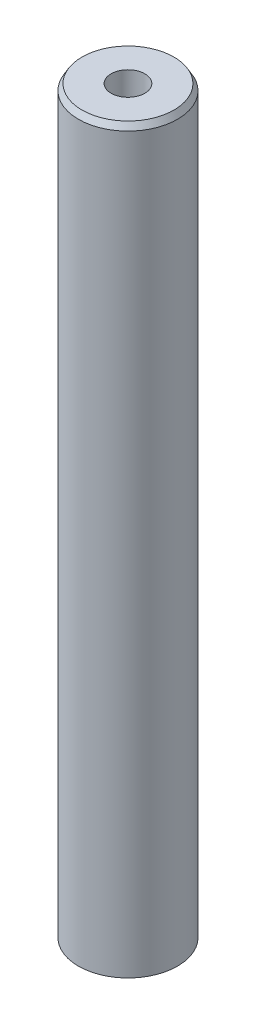
SolidWorks part; units mm, degrees
ref_plane "Front Plane" through (0, 0, 0) normal (0, 0, 1) x (1, 0, 0)
ref_plane "Top Plane" through (0, 0, 0) normal (0, 1, 0) x (1, 0, 0)
ref_plane "Right Plane" through (0, 0, 0) normal (1, 0, 0) x (0, 0, -1)
sketch "Sketch1" plane through (0, 0, 0) normal (0, 1, 0) x (1, 0, 0)
  circle A0 centre (0, 0) radius 40
  dimension "SHAFT_OD" = 80
extrude "Boss-Extrude1" add sketch "Sketch1" along normal blind 600
sketch "Sketch2" plane through (0, 0, 0) normal (0, 1, 0) x (1, 0, 0)
  circle A0 centre (0, 0) radius 13.6341
  dimension "BORE_D" = 27.2682
extrude "Cut-Extrude1" cut sketch "Sketch2" along normal through all
chamfer "Chamfer1" distance 5.0049 angle 30 2 edges at (0, 600, 40) (0, 0, 40) first distance on face at (0, 600, 40) first distance on face at (0, 0, 13.6341)
